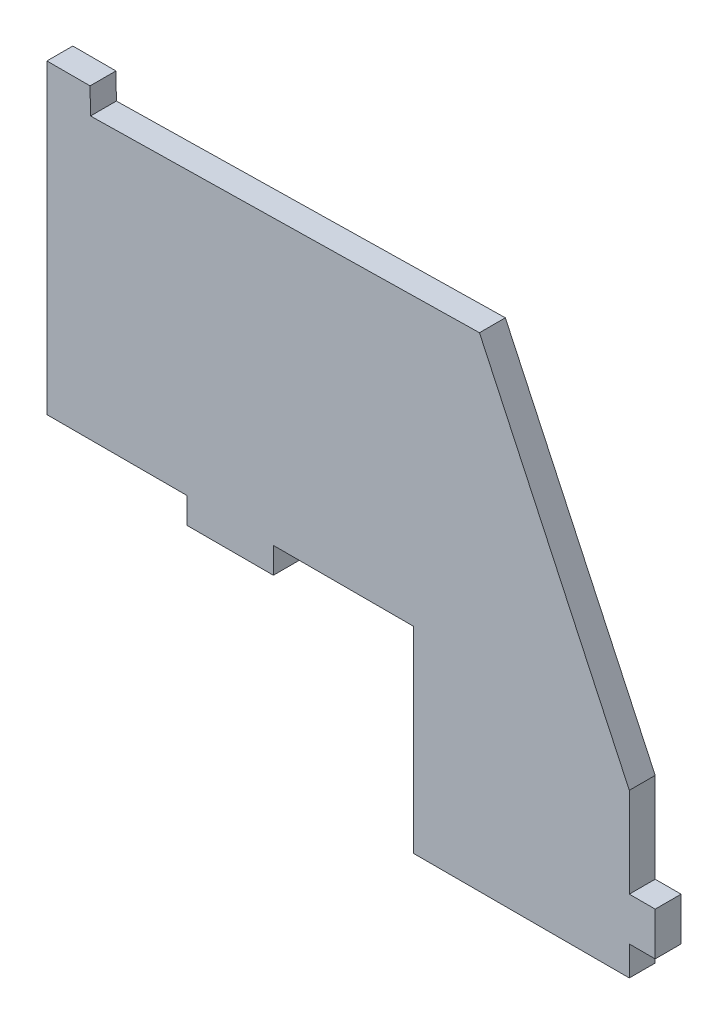
SolidWorks part; units mm, degrees
ref_plane "Plan de face" through (0, 0, 0) normal (0, 0, 1) x (1, 0, 0)
ref_plane "Plan de dessus" through (0, 0, 0) normal (0, 1, 0) x (1, 0, 0)
ref_plane "Plan de droite" through (0, 0, 0) normal (1, 0, 0) x (0, 0, -1)
sketch "Esquisse1" plane through (0, 0, 0) normal (0, 0, 1) x (1, 0, 0)
  line L0 (-76.0709, 85.2705) -> (-76.0709, 79.2724)
  line L1 (-76.0709, 85.2705) -> (-66.0709, 85.2705)
  line L2 (-66.0709, 85.2705) -> (-65.9662, 79.2724)
  line L4 (-65.9662, 79.2724) -> (24.1884, 80.846)
  line L5 (24.1884, 80.846) -> (58.9248, 6.3536)
  line L6 (8.9248, -31.3195) -> (8.9248, 14.2705)
  line L7 (58.9248, 6.3536) -> (58.9248, -31.3195)
  line L9 (58.9248, -31.3195) -> (8.9248, -31.3195)
  line L11 (8.9248, 14.2705) -> (-76.0709, 14.2705)
  line L12 (-76.0709, 14.2705) -> (-76.0709, 59.2724)
  line L14 (-76.0709, 59.2724) -> (-76.0709, 79.2724)
  dimension "D2" = 155
  dimension "D3" = 10
  dimension "D4" = 5.9982
  dimension "D5" = 37.6731
  dimension "D6" = 134.9957
  dimension "D7" = 50
  dimension "D9" = 114
  dimension "D11" = 116.59
  dimension "D12" = 20
  dimension "D13" = 5.9982
  dimension "D15" = 45.59
extrude "Boss.-Extru.2" add sketch "Esquisse1" along normal blind 6
sketch "Esquisse3" plane through (0, 0, 6) normal (0, 0, 1) x (1, 0, 0)
  line L0 (-76.0709, 14.2705) -> (8.9248, 14.2705) construction
  line L1 (-43.5752, 14.2705) -> (-23.5752, 14.2705)
  line L2 (-43.5752, 14.2705) -> (-43.5752, 8.2705)
  line L3 (-43.5752, 8.2705) -> (-23.5752, 8.2705)
  line L4 (-23.5752, 14.2705) -> (-23.5752, 8.2705)
  line L5 (8.9248, 14.2705) -> (8.9248, -31.3195) construction
  line L6 (58.9248, -31.3195) -> (58.9248, 6.3536) construction
  line L7 (58.9248, -24.4895) -> (64.9248, -24.4895)
  line L8 (58.9248, -24.4895) -> (58.9248, -14.4895)
  line L9 (58.9248, -14.4895) -> (64.9248, -14.4895)
  line L10 (64.9248, -24.4895) -> (64.9248, -14.4895)
  line L12 (8.9248, -31.3195) -> (58.9248, -31.3195) construction
  dimension "D1" = 20
  dimension "D2" = 6
  dimension "D3" = 32.5
  dimension "D4" = 6
  dimension "D5" = 10
  dimension "D6" = 6.83
extrude "Boss.-Extru.4" add sketch "Esquisse3" against normal blind 6
